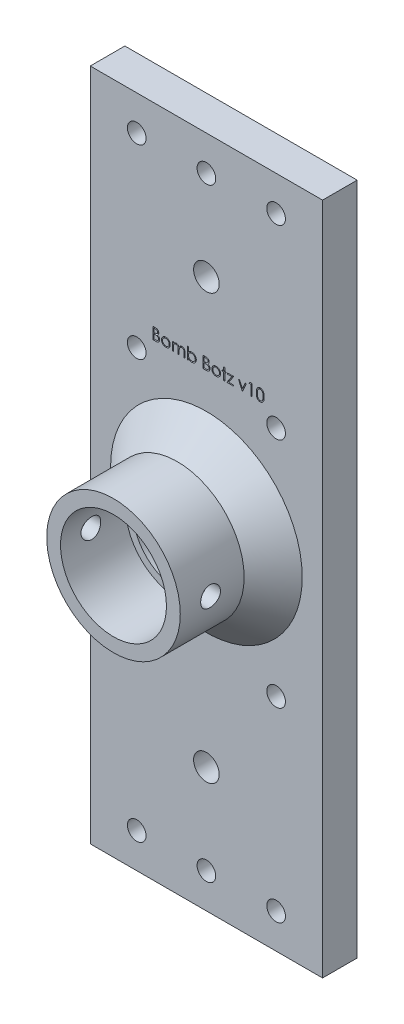
SolidWorks part; units mm, degrees
ref_plane "Front Plane" through (0, 0, 0) normal (0, 0, 1) x (1, 0, 0)
ref_plane "Top Plane" through (0, 0, 0) normal (0, 1, 0) x (1, 0, 0)
ref_plane "Right Plane" through (0, 0, 0) normal (1, 0, 0) x (0, 0, -1)
sketch "Sketch1" plane through (0, 0, 0) normal (0, 0, 1) x (1, 0, 0)
  line L5 (-31.75, 92.075) -> (31.75, 92.075)
  line L6 (-31.75, 92.075) -> (-31.75, -92.075)
  line L7 (-31.75, -92.075) -> (31.75, -92.075)
  line L8 (31.75, 92.075) -> (31.75, -92.075)
  line L9 (-31.75, 92.075) -> (31.75, -92.075) construction
  line L10 (-31.75, -92.075) -> (31.75, 92.075) construction
  point P5 (0, 0)
  dimension "D1" = 63.5
  dimension "D2" = 184.15
extrude "Boss-Extrude1" add sketch "Sketch1" along normal blind 4.7625 and the other way blind 4.699
sketch "Sketch3" plane through (0, 0, 4.7625) normal (0, 0, 1) x (1, 0, 0)
  circle A0 centre (0, 0) radius 6.35
  dimension "D1" = 12.7
extrude "Cut-Extrude1" cut sketch "Sketch3" against normal blind 0.508
sketch "Sketch4" plane through (0, 0, 4.7625) normal (0, 0, 1) x (1, 0, 0)
  circle A0 centre (0, 0) radius 18.2562
  dimension "D1" = 36.5125
extrude "Boss-Extrude2" add sketch "Sketch4" along normal blind 38.1 contours A0
sketch "Sketch5" plane through (0, 0, 42.8625) normal (0, 0, 1) x (1, 0, 0)
  circle A0 centre (0, 0) radius 12.4619
  dimension "D1" = 24.9237
extrude "Cut-Extrude2" cut sketch "Sketch5" against normal blind 38.1 contours A0
sketch "Sketch7" plane through (0, 0, 42.8625) normal (0, 0, 1) x (1, 0, 0)
  circle A0 centre (0, 0) radius 14.2875
  dimension "D1" = 28.575
extrude "Cut-Extrude3" cut sketch "Sketch7" against normal blind 30.48
hole_wizard "#10 Clearance Hole1" positions "Sketch8" profile "Sketch9" hole size "#10" standard "ANSI Inch" end condition up to next
sketch "Sketch8" plane through (0, 0, 4.7625) normal (0, 0, 1) x (1, 0, 0)
  line L0 (31.75, 92.075) -> (-31.75, 92.075) construction
  line L1 (31.75, -92.075) -> (31.75, 92.075) construction
  line L2 (-31.75, 92.075) -> (-31.75, -92.075) construction
  line L3 (-31.75, -92.075) -> (31.75, -92.075) construction
  point P0 (-19.05, 82.55)
  point P2 (-19.05, -82.55)
  point P4 (19.05, -82.55)
  point P6 (19.05, 82.55)
  point P23 (-19.05, 31.75)
  point P26 (-19.05, -31.75)
  point P28 (19.05, -31.75)
  point P30 (19.05, 31.75)
  point P31 (0, 82.55)
  point P33 (0, -82.55)
  dimension "D1" = 9.525
  dimension "D2" = 12.7
  dimension "D3" = 9.525
  dimension "D4" = 12.7
  dimension "D5" = 9.525
  dimension "D6" = 12.7
  dimension "D7" = 12.7
  dimension "D8" = 9.525
  dimension "D11" = 50.8
  dimension "D12" = 50.8
  dimension "D13" = 50.8
  dimension "D14" = 50.8
sketch "Sketch9" plane through (-19.05, 82.55, 4.7625) normal (1, 0, 0) x (0, -1, 0)
  line L0 (0, 0) -> (0, 9.4615)
  line L1 (0, 9.4615) -> (2.5527, 9.4615)
  line L2 (2.5527, 9.4615) -> (2.5527, 0)
  line L5 (2.5527, 0) -> (0, 0)
  line L11 (0, -6.35) -> (0, 107.95) construction
  dimension "Thru Hole Dia." = 5.1054
  dimension "Thru Hole Depth" = 9.4615
sketch "Sketch10" plane through (0, 0, 4.7625) normal (0, 0, 1) x (1, 0, 0)
  line L0 (31.75, 41.275) -> (-31.75, 41.275)
  line L1 (31.75, -92.075) -> (31.75, 92.075) construction
  line L2 (-31.75, 92.075) -> (-31.75, -92.075) construction
  line L3 (31.75, -41.275) -> (-31.75, -41.275)
  point P8 (-31.75, 0)
  dimension "D1" = 41.275
  dimension "D2" = 41.275
sketch "Sketch13" plane through (0, 0, 42.8625) normal (0, 0, 1) x (1, 0, 0)
  circle A0 centre (0, 0) radius 14.478
  dimension "D1" = 28.956
extrude "Cut-Extrude4" cut sketch "Sketch13" against normal up to surface (30.48 mm away) up to face at (14.2875, 0, 12.3825)
sketch "Sketch14" plane through (0, 0, 42.8625) normal (0, 0, 1) x (1, 0, 0)
  circle A0 centre (0, 0) radius 18.2562
extrude "Cut-Extrude5" cut sketch "Sketch14" against normal blind 12.7
sketch "Sketch15" plane through (0, -92.075, 0) normal (0, -1, 0) x (-1, 0, 0)
hole_wizard "#3 (0.213) Diameter Hole1" positions "3DSketch7" profile "Sketch22" hole size "#3" standard "ANSI Inch" end condition through all
sketch3d "3DSketch7"
  point P0 (18.2562, 0, 21.8735)
sketch "Sketch22" plane through (18.2562, 0, 21.8735) normal (0, 1, 0) x (0, 0, -1)
  line L0 (0, 0) -> (0, 50.0063)
  line L1 (0, 50.0063) -> (2.7051, 50.0063)
  line L2 (2.7051, 50.0063) -> (2.7051, 0)
  line L5 (2.7051, 0) -> (0, 0)
  line L11 (0, -6.35) -> (0, 107.95) construction
  dimension "Thru Hole Dia." = 5.4102
  dimension "Thru Hole Depth" = 50.0063
hole_wizard "CBORE for M6 Hex Head Bolt1" positions "Sketch25" profile "Sketch26" counterbore size "M6" standard "ANSI Metric" end condition through all
sketch "Sketch25" plane through (0, 0, -4.699) normal (0, 0, -1) x (-1, 0, 0)
  line L0 (-31.75, 41.275) -> (31.75, 41.275) construction
  line L1 (-31.75, -41.275) -> (31.75, -41.275) construction
  point P0 (0, -58.039)
  point P2 (0, 58.039)
  dimension "D1" = 16.764
  dimension "D2" = 16.764
sketch "Sketch26" plane through (0, -58.039, -4.699) normal (1, 0, 0) x (0, 1, 0)
  line L0 (0, 0) -> (0, 34.8615)
  line L1 (0, 34.8615) -> (3.5, 34.8615)
  line L3 (3.5, 34.8615) -> (3.5, 4.38)
  line L4 (3.5, 4.38) -> (7.275, 4.38)
  line L5 (7.275, 4.38) -> (7.275, 0)
  line L7 (7.275, 0) -> (0, 0)
  line L11 (0, -6.35) -> (0, 107.95) construction
  dimension "Thru Hole Dia." = 7
  dimension "Thru Hole Depth" = 34.8615
  dimension "C'Bore Dia." = 14.55
  dimension "C'Bore Depth" = 4.38
sketch "Sketch28" plane through (0, 0, 4.7625) normal (0, 0, 1) x (1, 0, 0)
  text T0 "Bomb Botz v10"
extrude "Boss-Extrude4" add sketch "Sketch28" against normal blind 1.27
chamfer "Chamfer1" distance 7.9375 distance2 7.9375 1 edges at (18.2562, 0, 4.7625)
sketch "Sketch29" plane through (0, 0, 4.7625) normal (0, 0, 1) x (1, 0, 0)
  text T0 "Bomb Botz v10"
extrude "Cut-Extrude6" cut sketch "Sketch29" against normal blind 1.27
